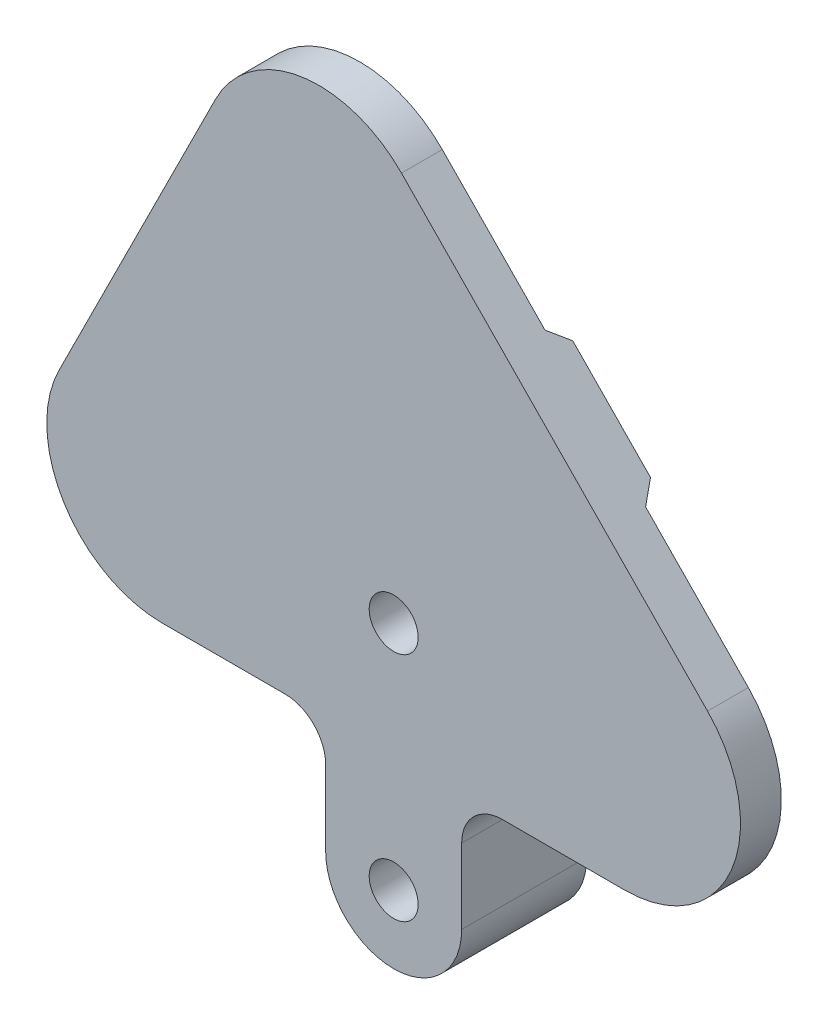
SolidWorks part; units mm, degrees
material "ABS"
ref_plane "Płaszczyzna przednia" through (0, 0, 0) normal (0, 0, 1) x (1, 0, 0)
ref_plane "Płaszczyzna górna" through (0, 0, 0) normal (0, 1, 0) x (1, 0, 0)
ref_plane "Płaszczyzna prawa" through (0, 0, 0) normal (1, 0, 0) x (0, 0, -1)
sketch "Szkic1" plane through (0, 0, 0) normal (0, 0, 1) x (1, 0, 0)
  line L0 (-7.6026, 3.8013) -> (3.8974, 26.8013)
  line L1 (17.5761, 28.944) -> (40.0761, 5.944)
  line L2 (34, -8.5) -> (25, -8.5)
  line L3 (22, -17) -> (22, -11.5)
  line L4 (12, -17) -> (12, -11.5)
  line L5 (9, -8.5) -> (0, -8.5)
  arc A0 (-7.6026, 3.8013) -> (0, -8.5) centre (0, 0) ccw
  arc A1 (17.5761, 28.944) -> (3.8974, 26.8013) centre (11.5, 23) ccw
  arc A2 (34, -8.5) -> (40.0761, 5.944) centre (34, 0) ccw
  circle A3 centre (17, 0) radius 1.8
  circle A4 centre (17, -17) radius 1.8
  arc A5 (12, -17) -> (22, -17) centre (17, -17) ccw
  arc A6 (12, -11.5) -> (9, -8.5) centre (9, -11.5) ccw
  arc A7 (22, -11.5) -> (25, -8.5) centre (25, -11.5) cw
  point P20 (12, -8.5)
  dimension "D1" = 17
  dimension "D2" = 17
  dimension "D3" = 3.6
  dimension "D4" = 34
  dimension "D5" = 17
  dimension "D6" = 23
  dimension "D7" = 17
  dimension "D8" = 11.5
  dimension "D10" = 23
  dimension "D11" = 17
  dimension "D12" = 3.6
  dimension "D14" = 5
  dimension "D15" = 3
  dimension "D9" = 23
  dimension "D13" = 17
extrude "Dodanie-wyciągnięcie1" add sketch "Szkic1" along normal blind 3
sketch "Szkic2" plane through (0, 0, 0) normal (0, 0, -1) x (-1, 0, 0)
  circle A0 centre (-34, 0) radius 6
  circle A1 centre (-11.5, 23) radius 6
  circle A2 centre (0, 0) radius 6
  dimension "D1" = 12
  dimension "D2" = 12
  dimension "D3" = 12
extrude "Wytnij-wyciągnięcie1" cut sketch "Szkic2" against normal blind 2
chamfer "Sfazowanie1" distance 0.5 angle 45 3 edges at (5.5, 23, 2) (-6, 0, 2) (28, 0, 2)
sketch "Szkic3" plane through (0, 0, 0) normal (0, 0, -1) x (-1, 0, 0)
  line L2 (-22, -17) -> (-22, 3.786)
  line L3 (-22.9021, 5.9305) -> (-31.6846, 14.522)
  line L4 (-25.9676, 20.366) -> (-16.0643, 10.678)
  line L5 (-40.0761, 5.944) -> (-17.5761, 28.944) construction
  line L6 (1.022, 16.9626) -> (-12.6248, 10.1392)
  line L7 (-3.8974, 26.8013) -> (7.6026, 3.8013) construction
  line L8 (2.6833, 13.64) -> (-10.3416, 7.1276)
  line L9 (-12, -17) -> (-12, 4.4443)
  line L10 (1.022, 16.9626) -> (2.6833, 13.64)
  line L11 (-25.9676, 20.366) -> (-31.6846, 14.522)
  arc A0 (-22, -17) -> (-12, -17) centre (-17, -17) ccw
  circle A2 centre (-17, 0) radius 1.8
  circle A3 centre (-17, -17) radius 1.8
  circle A4 centre (-34, 0) radius 5.5 construction
  circle A5 centre (-11.5, 23) radius 5.5 construction
  circle A6 centre (0, 0) radius 5.5 construction
  arc A7 (-10.3416, 7.1276) -> (-12, 4.4443) centre (-9, 4.4443) ccw
  arc A8 (-12.6248, 10.1392) -> (-16.0643, 10.678) centre (-13.9665, 12.8225) cw
  arc A9 (-22, 3.786) -> (-22.9021, 5.9305) centre (-25, 3.786) ccw
  dimension "D1" = 10
  dimension "D3" = 12
  dimension "D2" = 12
  dimension "D4" = 11
  dimension "D9" = 3
  dimension "D5" = 11
  dimension "D6" = 90
  dimension "D7" = 90
  dimension "D8" = 90
extrude "Dodanie-wyciągnięcie2" add sketch "Szkic3" along normal blind 1.2
chamfer "Sfazowanie2" distance 1.2 angle 45 9 edges at (12, -3.5279, 0) (22, -3.857, 0) (27.2933, 10.2262, 0) (22.2347, 4.9492, 0) (5.8014, 13.5509, 0) (14.4307, 9.8586, 0) (21.016, 15.522, 0) (3.8292, 10.3838, 0) (11.552, 6.0215, 0)
sketch "Szkic4" plane through (0, 0, -1.2) normal (0, 0, -1) x (-1, 0, 0)
  line L0 (-22, -12.1) -> (-12, -12.1)
  line L1 (-22, -12.1) -> (-22, -17)
  line L3 (-12, -12.1) -> (-12, -17)
  arc A0 (-22, -17) -> (-12, -17) centre (-17, -17) ccw
  circle A1 centre (-17, -17) radius 1.8
  dimension "D1" = 10
  dimension "D2" = 4.9
  dimension "D3" = 10
extrude "Dodanie-wyciągnięcie3" add sketch "Szkic4" along normal blind 5
